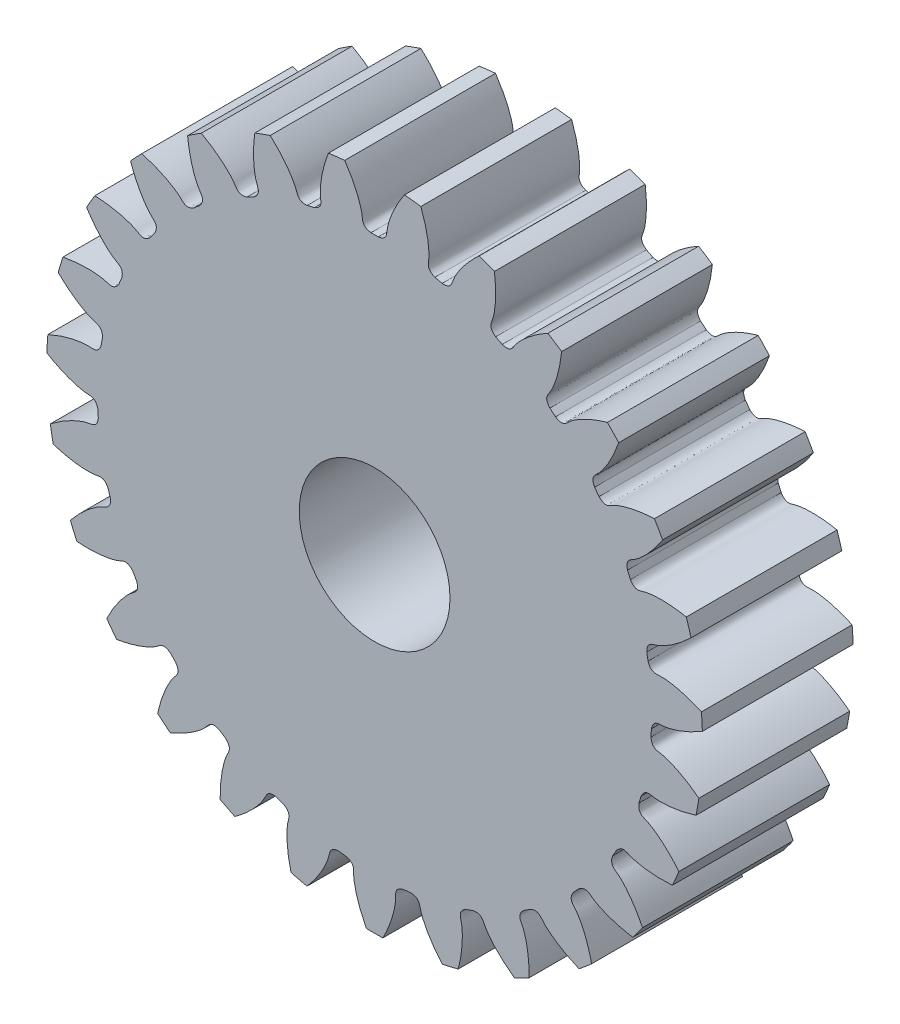
SolidWorks part; units mm, degrees
ref_plane "前视基准面" through (0, 0, 0) normal (0, 0, 1) x (1, 0, 0)
ref_plane "上视基准面" through (0, 0, 0) normal (0, 1, 0) x (1, 0, 0)
ref_plane "右视基准面" through (0, 0, 0) normal (1, 0, 0) x (0, 0, -1)
sketch "草图1" plane through (0, 0, 0) normal (0, 0, 1) x (1, 0, 0)
  circle A0 centre (0, 0) radius 8.7
extrude "凸台-拉伸1" add sketch "草图1" along normal blind 4
ref_axis "基准轴1" through (0, 0, 4) along (0, 0, -1)
sketch "草图2" plane through (0, 0, 0) normal (0, 0, 1) x (1, 0, 0)
  line L0 (0, 0) -> (0, 8.7) construction
  circle A0 centre (0, 0) radius 8.7 construction
  arc A1 (0.0972, 7.3494) -> (-0.0972, 7.3494) centre (0, 0) ccw
  arc A2 (1.9259, 9.8527) -> (-1.9259, 9.8527) centre (0, 0) ccw
  spline S0 degree 3 poles (0.0972, 7.3494) (0.3321, 7.3872) (0.315, 7.5231) (0.3364, 7.6597) (0.3398, 7.6792) (0.3442, 7.7016) (0.3497, 7.7269) (0.3564, 7.7551) (0.3644, 7.786) (0.3739, 7.8197) (0.3849, 7.8562) (0.3976, 7.8953) (0.412, 7.937) (0.4284, 7.9813) (0.4467, 8.028) (0.4672, 8.0772) (0.4898, 8.1288) (0.5147, 8.1827) (0.5421, 8.2388) (0.5719, 8.2971) (0.6044, 8.3574) (0.6395, 8.4197) (0.6775, 8.4839) (0.7183, 8.55) (0.7621, 8.6178) (0.8089, 8.6872) (0.8589, 8.7581) (0.912, 8.8305) (0.9685, 8.9043) (1.0283, 8.9792) (1.0916, 9.0553) (1.1583, 9.1324) (1.2286, 9.2105) (1.3026, 9.2893) (1.3802, 9.3688) (1.4616, 9.4489) (1.5468, 9.5295) (1.6358, 9.6103) (1.7612, 9.7197) (1.8589, 9.7999) (1.9259, 9.8527) knots 0 0 0 0 0.119962 0.125269 0.131541 0.138778 0.14698 0.156147 0.166279 0.177376 0.189438 0.202465 0.216457 0.231414 0.247336 0.264222 0.282074 0.300891 0.320672 0.341419 0.36313 0.385807 0.409448 0.434054 0.459626 0.486162 0.513663 0.542129 0.57156 0.601956 0.633317 0.665643 0.698934 0.73319 0.768411 0.804597 0.841747 0.879863 0.918944 1 1 1 1
  spline S1 degree 3 poles (-0.0972, 7.3494) (-0.3321, 7.3872) (-0.315, 7.5231) (-0.3364, 7.6597) (-0.3398, 7.6792) (-0.3442, 7.7016) (-0.3497, 7.7269) (-0.3564, 7.7551) (-0.3644, 7.786) (-0.3739, 7.8197) (-0.3849, 7.8562) (-0.3976, 7.8953) (-0.412, 7.937) (-0.4284, 7.9813) (-0.4467, 8.028) (-0.4672, 8.0772) (-0.4898, 8.1288) (-0.5147, 8.1827) (-0.5421, 8.2388) (-0.5719, 8.2971) (-0.6044, 8.3574) (-0.6395, 8.4197) (-0.6775, 8.4839) (-0.7183, 8.55) (-0.7621, 8.6178) (-0.8089, 8.6872) (-0.8589, 8.7581) (-0.912, 8.8305) (-0.9685, 8.9043) (-1.0283, 8.9792) (-1.0916, 9.0553) (-1.1583, 9.1324) (-1.2286, 9.2105) (-1.3026, 9.2893) (-1.3802, 9.3688) (-1.4616, 9.4489) (-1.5468, 9.5295) (-1.6358, 9.6103) (-1.7612, 9.7197) (-1.8589, 9.7999) (-1.9259, 9.8527) knots 0 0 0 0 0.119962 0.125269 0.131541 0.138778 0.14698 0.156147 0.166279 0.177376 0.189438 0.202465 0.216457 0.231414 0.247336 0.264222 0.282074 0.300891 0.320672 0.341419 0.36313 0.385807 0.409448 0.434054 0.459626 0.486162 0.513663 0.542129 0.57156 0.601956 0.633317 0.665643 0.698934 0.73319 0.768411 0.804597 0.841747 0.879863 0.918944 1 1 1 1
extrude "切除-拉伸1" cut sketch "草图2" along normal through all
pattern_circular "阵列(圆周)1" count 27 every 13.333 about axis through (0, 0, 4) along (0, 0, -1) of "切除-拉伸1"
sketch "草图3" plane through (0, 0, 0) normal (0, 0, 1) x (1, 0, 0)
  circle A0 centre (0, 0) radius 8.1 construction
  dimension "Dn" = 16.2
sketch "草图4" plane through (0, 0, 4) normal (0, 0, 1) x (1, 0, 0)
  circle A0 centre (0, 0) radius 2
  dimension "D1" = 4
extrude "切除-拉伸2" cut sketch "草图4" against normal through all
